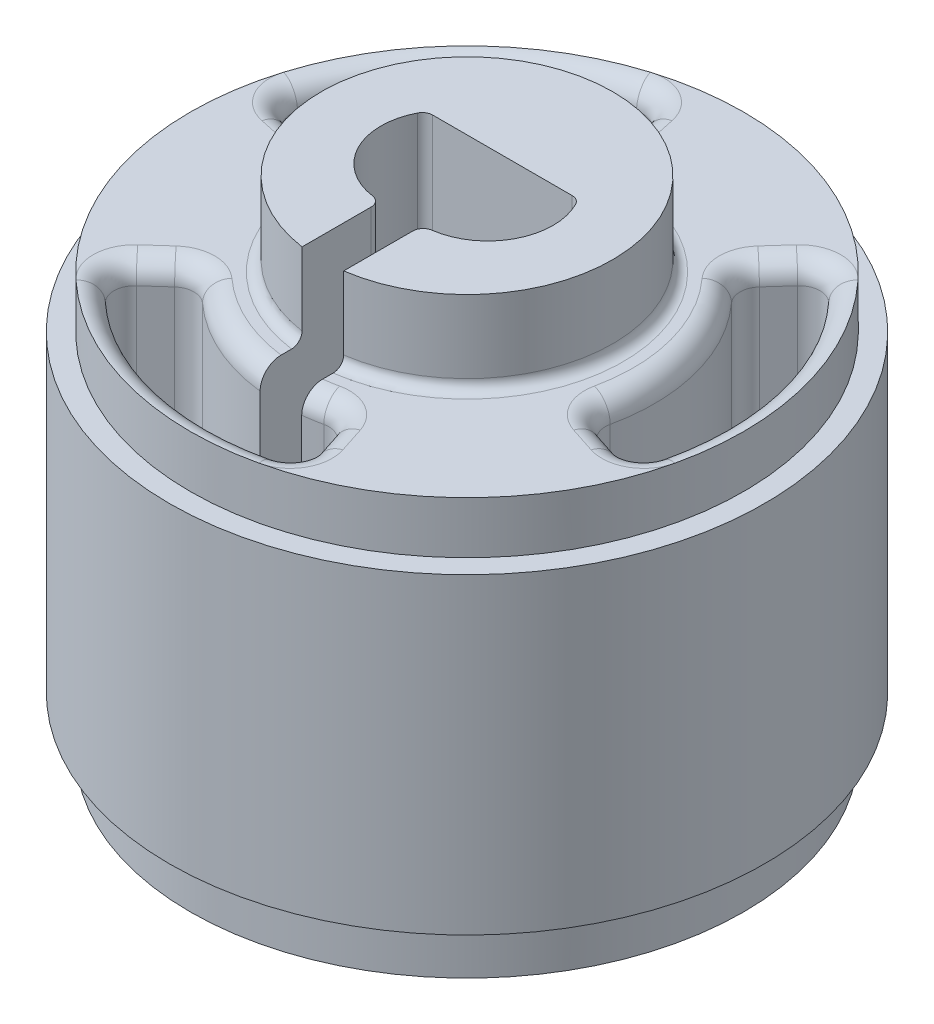
SolidWorks part; units mm, degrees
material "Nylon 101"
ref_plane "Front" through (0, 0, 0) normal (0, 0, 1) x (1, 0, 0)
ref_plane "Top" through (0, 0, 0) normal (0, 1, 0) x (1, 0, 0)
ref_plane "Right" through (0, 0, 0) normal (1, 0, 0) x (0, 0, -1)
sketch "Sketch1" plane through (0, 0, 0) normal (1, 0, 0) x (0, 0, -1)
  line L0 (0, 7.6229) -> (0, -6.4854) construction
  line L1 (0, -6) -> (6.65, -6)
  line L2 (6.65, -6) -> (6.65, -4.75)
  line L3 (6.65, -4.75) -> (7.15, -4.75)
  line L4 (7.15, -4.75) -> (7.15, 2.75)
  line L5 (7.15, 2.75) -> (6.65, 2.75)
  line L6 (6.65, 2.75) -> (6.65, 4)
  line L7 (6.65, 4) -> (3.5, 4)
  line L8 (3.5, 4) -> (3.5, 6)
  line L9 (3.5, 6) -> (0, 6)
  line L10 (0, -6) -> (0, 6)
  point P14 (0, 0)
  dimension "D1" = 10
  dimension "D2" = 7.5
  dimension "D3" = 7
  dimension "D4" = 2
  dimension "D5" = 7.15
  dimension "D6" = 0.5
revolve "Revolve1" add sketch "Sketch1" angle 360 about L0
sketch "Sketch2" plane through (0, 4, 0) normal (0, 1, 0) x (1, 0, 0)
  line L0 (0, 22.4874) -> (0, -21.7034) construction
  line L1 (-16.3723, 0) -> (20.3716, 0) construction
  line L2 (-1.2787, 6.0156) -> (-0.9356, 4.4017)
  line L3 (-6.0156, 1.2787) -> (-4.4017, 0.9356)
  arc A1 (-6.0156, 1.2787) -> (-1.2787, 6.0156) centre (0, 0) cw
  circle A2 centre (0, 0) radius 4.5
  arc A3 (-0.9356, 4.4017) -> (-4.4017, 0.9356) centre (0, 0) ccw
  circle A4 centre (0, 0) radius 6.65 construction
  dimension "D2" = 0.5
  dimension "D3" = 12
  dimension "D4" = 12
  dimension "D1" = 1
extrude "Cut-Extrude1" cut sketch "Sketch2" against normal through all
fillet "Fillet1" radius 0.5 4 edges at (-4.4017, -1, -0.9356) (-0.9356, -1, -4.4017) (-6.0156, -1, -1.2787) (-1.2787, -1, -6.0156)
fillet "Fillet2" radius 0.5 16 edges at (-5.8319, 4, -1.4057) (-4.3487, 4, -4.3487) (-1.4057, 4, -5.8319) (-1.1022, 4, -5.1855) (-1.091, 4, -4.5113) (-3.182, 4, -3.182) (-4.5113, 4, -1.091) (-5.1855, 4, -1.1022) (-1.091, -6, -4.5113) (-3.182, -6, -3.182) (-4.5113, -6, -1.091) (-5.1855, -6, -1.1022) (-5.8319, -6, -1.4057) (-4.3487, -6, -4.3487) (-1.4057, -6, -5.8319) (-1.1022, -6, -5.1855)
ref_axis "Axis1" through (0, 50, 0) along (0, -1, 0)
pattern_circular "CirPattern1" count 3 over 360 about axis through (0, 50, 0) along (0, -1, 0) of "Cut-Extrude1", "Fillet1", "Fillet2"
sketch "Sketch3" plane through (0, 6, 0) normal (0, 1, 0) x (1, 0, 0)
  line L0 (0, 0) -> (0, 1.7) construction
  line L1 (-0.5, -5.57) -> (-0.5, -1.57)
  line L2 (-1.82, 0.85) -> (1.82, 0.85)
  line L3 (0.5, -5.57) -> (0.5, -1.57)
  line L5 (-0.5, -5.57) -> (0.5, -5.57)
  arc A0 (-3.0263, -3.3304) -> (0.9556, -4.3974) centre (0, 0) ccw construction
  arc A1 (-3.0263, -3.3304) -> (0.9556, -4.3974) centre (0, 0) ccw construction
  arc A2 (-0.5, -1.57) -> (-1.82, 0.85) centre (-0.5, 0) cw
  arc A3 (0.5, -1.57) -> (1.82, 0.85) centre (0.5, 0) ccw
  point P15 (0, 0.85)
  dimension "D2" = 1.57
  dimension "D1" = 2.42
  dimension "D3" = 0.5
  dimension "D4" = 4
  dimension "D5" = 0.5
extrude "Cut-Extrude3" cut sketch "Sketch3" against normal through all
fillet "Fillet3" radius 0.25 4 edges at (0.5, 0, 1.57) (-0.5, 0, 1.57) (-1.82, 0, -0.85) (1.82, 0, -0.85)
fillet "Fillet4" radius 0.25 1 edges at (0, 4, -3.5)
